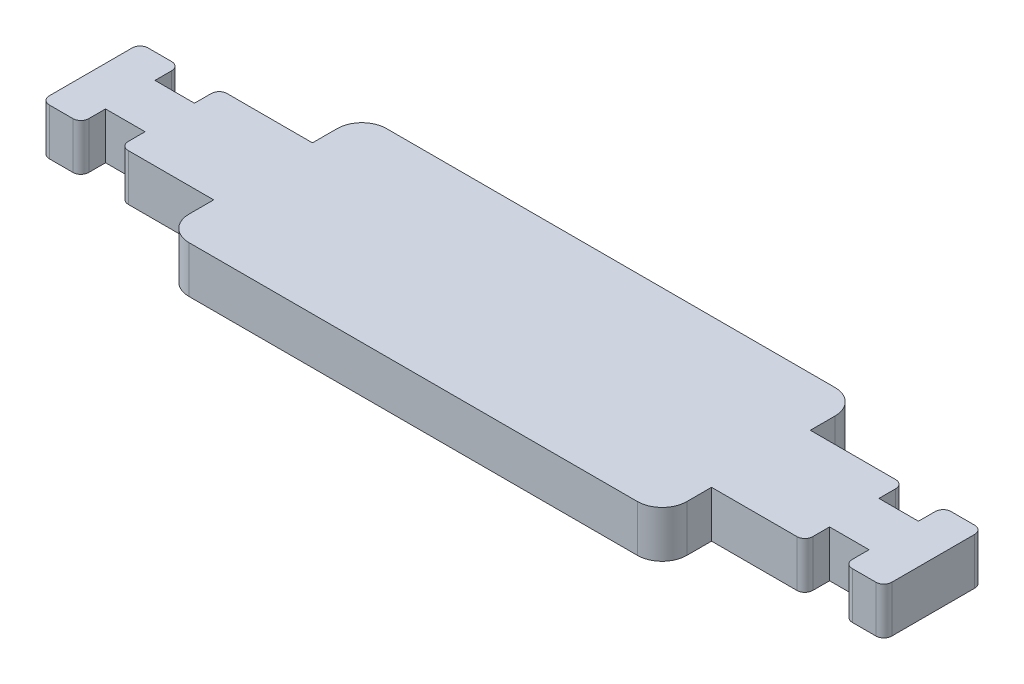
SolidWorks part; units mm, degrees
ref_plane "Front Plane" through (0, 0, 0) normal (0, 0, 1) x (1, 0, 0)
ref_plane "Top Plane" through (0, 0, 0) normal (0, 1, 0) x (1, 0, 0)
ref_plane "Right Plane" through (0, 0, 0) normal (1, 0, 0) x (0, 0, -1)
sketch "Sketch3" plane through (0, 0, 0) normal (0, 1, 0) x (1, 0, 0)
  line L0 (0, -17.5593) -> (0, 17.5593) construction
  line L1 (-19.05, 17.5593) -> (-16.05, 17.5593)
  line L2 (-19.05, 17.5593) -> (-19.05, -17.5593)
  line L3 (-19.05, -17.5593) -> (-16.05, -17.5593)
  line L4 (-16.05, 17.5593) -> (-16.05, -17.5593)
  line L5 (-19.05, 17.5593) -> (-16.05, -17.5593) construction
  line L6 (-19.05, -17.5593) -> (-16.05, 17.5593) construction
  line L7 (19.05, -17.5593) -> (16.05, 17.5593) construction
  line L8 (19.05, 17.5593) -> (16.05, -17.5593) construction
  line L9 (16.05, 17.5593) -> (16.05, -17.5593)
  line L10 (19.05, -17.5593) -> (16.05, -17.5593)
  line L11 (19.05, 17.5593) -> (19.05, -17.5593)
  line L12 (19.05, 17.5593) -> (16.05, 17.5593)
  point P0 (-17.55, 0)
  point P12 (17.55, 0)
  dimension "D1" = 3
  dimension "D2" = 38.1
sketch "Sketch1" plane through (0, 0, 0) normal (0, 1, 0) x (1, 0, 0)
  line L1 (14.4145, -6.35) -> (-14.4145, -6.35)
  line L2 (16.002, -4.7625) -> (16.002, 4.7625)
  line L3 (14.4145, 6.35) -> (-14.4145, 6.35)
  line L4 (-16.002, -4.7625) -> (-16.002, 4.7625)
  line L5 (16.002, -6.35) -> (-16.002, 6.35) construction
  line L6 (16.002, 6.35) -> (-16.002, -6.35) construction
  arc A0 (16.002, 4.7625) -> (14.4145, 6.35) centre (14.4145, 4.7625) ccw
  arc A1 (16.002, -4.7625) -> (14.4145, -6.35) centre (14.4145, -4.7625) cw
  arc A2 (-14.4145, -6.35) -> (-16.002, -4.7625) centre (-14.4145, -4.7625) cw
  arc A3 (-14.4145, 6.35) -> (-16.002, 4.7625) centre (-14.4145, 4.7625) ccw
  point P0 (0, 0)
  dimension "D3" = 1.5875
  dimension "D1" = 32.004
  dimension "D2" = 12.7
extrude "Boss-Extrude1" add sketch "Sketch1" along normal mid plane 3
sketch "Sketch2" plane through (0, 1.5, 0) normal (0, 1, 0) x (1, 0, 0)
  line L0 (-16.002, 4.7625) -> (-16.002, -4.7625) construction
  line L1 (-22.002, -3.175) -> (-16.002, -3.175)
  line L2 (-22.002, 1.5875) -> (-22.002, 3.175)
  line L3 (-22.002, 3.175) -> (-16.002, 3.175)
  line L4 (-16.002, -3.175) -> (-16.002, 3.175)
  line L5 (-22.002, -3.175) -> (-16.002, 3.175) construction
  line L6 (-22.002, 3.175) -> (-16.002, -3.175) construction
  line L7 (-22.002, -3.175) -> (-24.542, -3.175) construction
  line L13 (-24.542, -3.175) -> (-27.082, -3.175)
  line L14 (-27.082, -3.175) -> (-27.082, 3.175)
  line L15 (-27.082, 3.175) -> (-24.542, 3.175)
  line L16 (-24.542, 3.175) -> (-24.542, 1.5875)
  line L17 (-24.542, 1.5875) -> (-22.002, 1.5875)
  line L18 (-22.002, -1.5875) -> (-22.002, 1.5875) construction
  line L19 (-22.002, -3.175) -> (-22.002, -1.5875)
  line L20 (-22.002, -1.5875) -> (-24.542, -1.5875)
  line L21 (-24.542, -1.5875) -> (-24.542, -3.175)
  point P0 (-19.002, 0)
  point P5 (-16.5382, 0)
  dimension "D3" = 1.5875
  dimension "D1" = 6.35
  dimension "D2" = 6
  dimension "D4" = 2.54
  dimension "D5" = 2.54
extrude "Boss-Extrude2" add sketch "Sketch2" against normal up to surface (3 mm away) up to face at (0, -1.5, 0)
fillet "Fillet1" radius 0.508 6 edges at (-27.082, 0, 3.175) (-27.082, 0, -3.175) (-24.542, 0, -3.175) (-22.002, 0, -3.175) (-22.002, 0, 3.175) (-24.542, 0, 3.175)
mirror "Mirror1" about plane through (0, 0, 0) normal (1, 0, 0) of bodies 102
equation "\"D1@Sketch3\"=3mm"
equation "\"D1@Sketch1\"=1.25in+.01in"
equation "\"D2@Sketch2\"=6mm"
